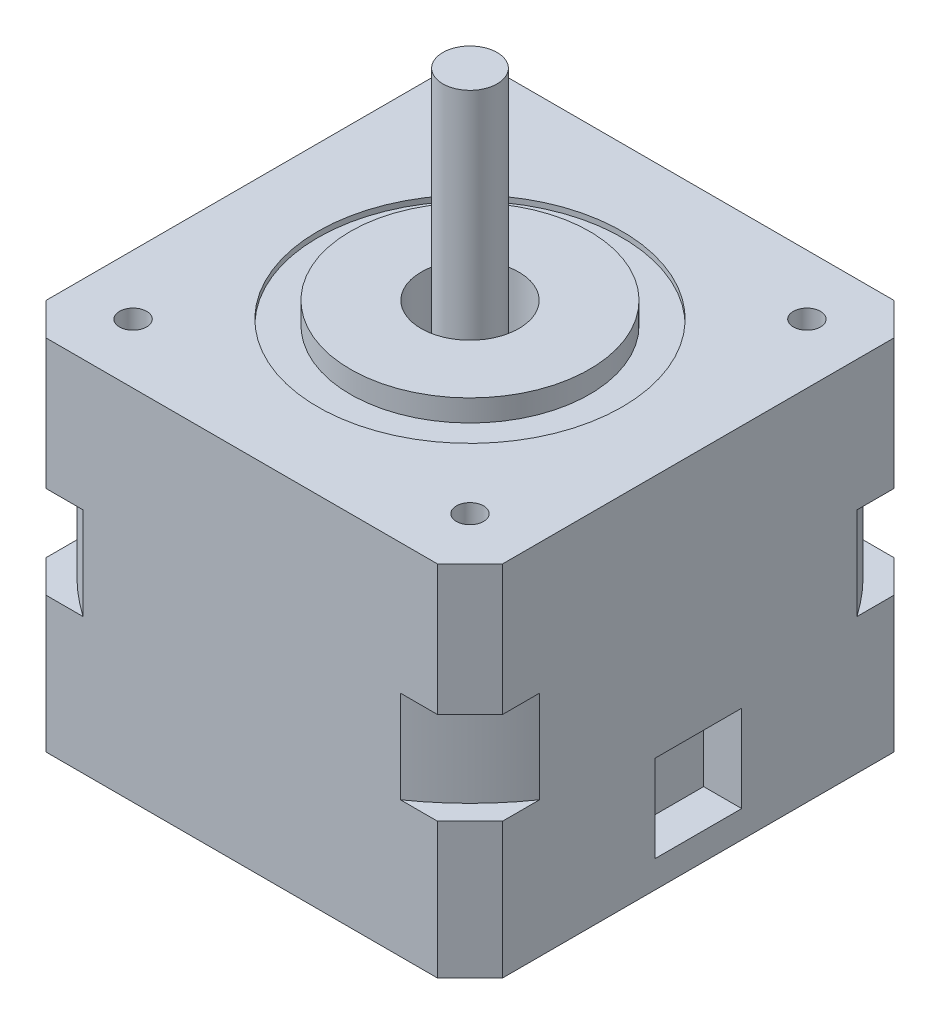
SolidWorks part; units mm, degrees
ref_plane "Front Plane" through (0, 0, 0) normal (0, 0, 1) x (1, 0, 0)
ref_plane "Top Plane" through (0, 0, 0) normal (0, 1, 0) x (1, 0, 0)
ref_plane "Right Plane" through (0, 0, 0) normal (1, 0, 0) x (0, 0, -1)
sketch "Sketch1" plane through (0, 0, 0) normal (0, 1, 0) x (1, 0, 0)
  line L0 (-18, 21) -> (-21, 18)
  line L1 (18, 21) -> (-18, 21)
  line L2 (21, 18) -> (21, -18)
  line L3 (18, -21) -> (-18, -21)
  line L4 (-21, 18) -> (-21, -18)
  line L5 (21, 21) -> (-21, -21) construction
  line L6 (21, -21) -> (-21, 21) construction
  line L7 (-21, -18) -> (-18, -21)
  line L8 (21, -18) -> (18, -21)
  line L9 (21, 18) -> (18, 21)
  point P0 (0, 0)
  point P14 (-21, -11.1783)
  dimension "D1" = 42
  dimension "D2" = 42
extrude "Boss-Extrude1" add sketch "Sketch1" along normal blind 33
ref_plane "Plane1" through (0, 0, 0) normal (0.7071, 0, 0.7071) x (0.7071, 0, -0.7071)
sketch "Sketch3" plane through (0, 0, 0) normal (0.7071, 0, 0.7071) x (0.7071, 0, -0.7071)
  line L0 (0, 33) -> (0, 0) construction
  line L1 (-2.1213, 33) -> (2.1213, 33) construction
  line L2 (27.5772, 21) -> (25.5772, 21)
  line L3 (27.5772, 33) -> (27.5772, 0) construction
  line L4 (25.5772, 21) -> (25.5772, 12.5)
  line L5 (25.5772, 12.5) -> (27.5772, 12.5)
  line L6 (2.1213, 0) -> (27.5772, 0) construction
  line L7 (2.1213, 33) -> (27.5772, 33) construction
  line L8 (14, 33) -> (14, 32.5)
  line L9 (27.5772, 21) -> (29.3552, 21)
  line L10 (29.3552, 21) -> (29.3552, 12.5)
  line L11 (29.3552, 12.5) -> (27.5772, 12.5)
  line L12 (14, 32.5) -> (11, 32.5)
  line L13 (11, 32.5) -> (11, 33)
  line L14 (11, 33) -> (14, 33)
  line L15 (4.5, 33) -> (4.5, 28)
  line L16 (4.5, 28) -> (0, 28)
  line L17 (0, 33) -> (4.5, 33)
  point P10 (26.5772, 12.5)
  dimension "D1" = 12.5
  dimension "D2" = 12
  dimension "D3" = 2
  dimension "D4" = 1.778
  dimension "D5" = 0.5
  dimension "D6" = 11
  dimension "D7" = 3
  dimension "D8" = 4.5
  dimension "D9" = 5
revolve "Cut-Revolve2" cut sketch "Sketch3" angle 360 about L0 region at (1.591, 30.5, -1.591) region at (19.4215, 16.75, -19.4215)
sketch "Sketch4" plane through (0, 33, 0) normal (0, 1, 0) x (1, 0, 0)
  line L1 (15.5, -15.5) -> (-15.5, -15.5) construction
  line L2 (15.5, -15.5) -> (15.5, 15.5) construction
  line L3 (15.5, 15.5) -> (-15.5, 15.5) construction
  line L4 (-15.5, -15.5) -> (-15.5, 15.5) construction
  line L5 (15.5, -15.5) -> (-15.5, 15.5) construction
  line L6 (15.5, 15.5) -> (-15.5, -15.5) construction
  circle A0 centre (-15.5, 15.5) radius 1.25
  circle A1 centre (15.5, 15.5) radius 1.25
  circle A2 centre (15.5, -15.5) radius 1.25
  circle A3 centre (-15.5, -15.5) radius 1.25
  point P0 (0, 0)
  dimension "D1" = 2.5
  dimension "D2" = 28.5
extrude "Cut-Extrude1" cut sketch "Sketch4" against normal through all
sketch "Sketch5" plane through (0, 0, 0) normal (0, -1, 0) x (1, 0, 0)
  circle A4 centre (-15.5, -15.5) radius 1.25 construction
  circle A5 centre (15.5, -15.5) radius 1.25 construction
  circle A6 centre (15.5, 15.5) radius 1.25 construction
  circle A7 centre (-15.5, 15.5) radius 1.25 construction
  circle A8 centre (-15.5, 15.5) radius 3.25
  circle A9 centre (-15.5, -15.5) radius 3.25
  circle A10 centre (15.5, -15.5) radius 3.25
  circle A11 centre (15.5, 15.5) radius 3.25
  circle A12 centre (0, 0) radius 4.75
  circle A13 centre (15.5, 15.5) radius 1.25 construction
  circle A14 centre (-15.5, 15.5) radius 1.25 construction
  circle A15 centre (-15.5, -15.5) radius 1.25 construction
  circle A16 centre (15.5, -15.5) radius 1.25 construction
  point P5 (15.5, 15.5)
  dimension "D1" = 6.5
  dimension "D2" = 9.5
extrude "Cut-Extrude2" cut sketch "Sketch5" against normal blind 3.5
sketch "Sketch6" plane through (21, 0, 0) normal (1, 0, 0) x (0, 0, -1)
  line L1 (-4, 2.5) -> (4, 2.5)
  line L2 (-4, 2.5) -> (-4, 10.5)
  line L3 (-4, 10.5) -> (4, 10.5)
  line L4 (4, 2.5) -> (4, 10.5)
  line L5 (-18, 0) -> (18, 0) construction
  point P4 (-4, 1.8272)
  point P6 (0, 10.5)
  point P8 (5.4752, 9.2137)
  dimension "D1" = 8
  dimension "D2" = 2.5
extrude "Cut-Extrude3" cut sketch "Sketch6" against normal blind 3.5
sketch "Sketch7" plane through (0, 0, 0) normal (0.7071, 0, 0.7071) x (0.7071, 0, -0.7071)
  line L0 (0, 33) -> (0, 0) construction
  line L1 (-2.1213, 33) -> (2.1213, 33) construction
  line L2 (4.5, 34.5) -> (11, 34.5)
  line L3 (11, 34.5) -> (11, 33)
  line L4 (2.1213, 33) -> (27.5772, 33) construction
  line L6 (4.5, 34.5) -> (4.5, 33)
  line L7 (4.5, 33) -> (11, 33)
  line L8 (0, 53) -> (2.5, 53)
  line L9 (2.5, 53) -> (2.5, 28)
  line L10 (4.5, 28) -> (-4.5, 28) construction
  line L11 (2.5, 28) -> (0, 28)
  line L13 (0, 53) -> (0, 28)
  dimension "D1" = 1.5
  dimension "D2" = 2.5
  dimension "D3" = 25
revolve "Revolve1" add sketch "Sketch7" angle 360 about L0
sketch "Sketch8" plane through (0, 0, 0) normal (0, -1, 0) x (1, 0, 0)
  circle A1 centre (-15.5, 15.5) radius 1.25 construction
  circle A2 centre (-15.5, 15.5) radius 1.25
  circle A3 centre (-15.5, -15.5) radius 1.25 construction
  circle A4 centre (15.5, -15.5) radius 1.25 construction
  circle A5 centre (15.5, 15.5) radius 1.25 construction
  circle A6 centre (-15.5, -15.5) radius 1.25
  circle A7 centre (15.5, -15.5) radius 1.25
  circle A8 centre (15.5, 15.5) radius 1.25
  circle A23 centre (-15.5, 15.5) radius 2.742
  circle A24 centre (-15.5, 15.5) radius 2.742
  circle A26 centre (-15.5, -15.5) radius 2.742
  circle A27 centre (-15.5, -15.5) radius 2.742
  circle A29 centre (15.5, -15.5) radius 2.742
  circle A30 centre (15.5, -15.5) radius 2.742
  circle A32 centre (15.5, 15.5) radius 2.742
  circle A33 centre (15.5, 15.5) radius 2.742
  dimension "D1" = 0.508
  dimension "D3" = 0.508
  dimension "D4" = 0.508
  dimension "D5" = 0.508
extrude "Boss-Extrude2" add sketch "Sketch8" against normal offset from surface (2.992 mm away) 0.508 separate body contours A2 | A24 A2 | A33 A8 | A8 | A30 A7 | A7 | A27 A6 | A6 region at (-15.5, 0, 15.5) region at (-15.5, 0, -15.5) region at (15.5, 0, -15.5) region at (15.5, 0, 15.5) region at (-18.1644, 0, 15.5) region at (-18.1644, 0, -15.5) region at (12.8356, 0, -15.5) region at (12.8356, 0, 15.5) up to face at (-15.5, 3.5, 12.25)
extrude "Boss-Extrude3" add sketch "Sketch8<3>" against normal blind 21.336 contours A2 | A6 | A7 | A8 region at (-15.5, 0, 15.5) region at (-15.5, 0, -15.5) region at (15.5, 0, -15.5) region at (15.5, 0, 15.5)
sketch "Sketch8<3>" plane through (0, 0, 0) normal (0, -1, 0) x (1, 0, 0) same geometry as "Sketch8"
sketch "Sketch9" plane through (0, 0, 0) normal (0, -1, 0) x (1, 0, 0)
  line L0 (18.242, -15.5) -> (12.758, -15.5) construction
  line L1 (15.5, -18.242) -> (15.5, -12.758) construction
  line L2 (18.134, -16.262) -> (16.262, -16.262)
  line L3 (16.262, -16.262) -> (16.262, -18.134)
  line L4 (16.262, -14.738) -> (16.262, -12.866)
  line L5 (18.134, -14.738) -> (16.262, -14.738)
  line L6 (14.738, -16.262) -> (14.738, -18.134)
  line L7 (12.866, -16.262) -> (14.738, -16.262)
  line L8 (14.738, -14.738) -> (14.738, -12.866)
  line L9 (12.866, -14.738) -> (14.738, -14.738)
  line L10 (0, -21) -> (0, 21) construction
  line L11 (18, -21) -> (-18, -21) construction
  line L12 (-18, 21) -> (18, 21) construction
  line L13 (21, 0) -> (-21, 0) construction
  line L14 (21, 18) -> (21, -18) construction
  line L15 (-21, -18) -> (-21, 18) construction
  line L16 (-15.5, -18.242) -> (-15.5, -12.758) construction
  line L17 (-18.242, -15.5) -> (-12.758, -15.5) construction
  line L18 (-12.866, -14.738) -> (-14.738, -14.738)
  line L19 (-14.738, -14.738) -> (-14.738, -12.866)
  line L20 (-12.866, -16.262) -> (-14.738, -16.262)
  line L21 (-14.738, -16.262) -> (-14.738, -18.134)
  line L22 (-18.134, -14.738) -> (-16.262, -14.738)
  line L23 (-16.262, -14.738) -> (-16.262, -12.866)
  line L24 (-16.262, -16.262) -> (-16.262, -18.134)
  line L25 (-18.134, -16.262) -> (-16.262, -16.262)
  line L26 (-18.242, 15.5) -> (-12.758, 15.5) construction
  line L27 (-15.5, 18.242) -> (-15.5, 12.758) construction
  line L28 (-18.134, 16.262) -> (-16.262, 16.262)
  line L29 (-16.262, 16.262) -> (-16.262, 18.134)
  line L30 (-16.262, 14.738) -> (-16.262, 12.866)
  line L31 (-18.134, 14.738) -> (-16.262, 14.738)
  line L32 (-14.738, 16.262) -> (-14.738, 18.134)
  line L33 (-12.866, 16.262) -> (-14.738, 16.262)
  line L34 (-14.738, 14.738) -> (-14.738, 12.866)
  line L35 (-12.866, 14.738) -> (-14.738, 14.738)
  line L36 (15.5, 18.242) -> (15.5, 12.758) construction
  line L37 (18.242, 15.5) -> (12.758, 15.5) construction
  line L38 (12.866, 14.738) -> (14.738, 14.738)
  line L39 (14.738, 14.738) -> (14.738, 12.866)
  line L40 (12.866, 16.262) -> (14.738, 16.262)
  line L41 (14.738, 16.262) -> (14.738, 18.134)
  line L42 (18.134, 14.738) -> (16.262, 14.738)
  line L43 (16.262, 14.738) -> (16.262, 12.866)
  line L44 (16.262, 16.262) -> (16.262, 18.134)
  line L45 (18.134, 16.262) -> (16.262, 16.262)
  circle A0 centre (15.5, -15.5) radius 2.742 construction
  circle A1 centre (15.5, -15.5) radius 2.742
  circle A2 centre (-15.5, -15.5) radius 2.742
  circle A3 centre (-15.5, 15.5) radius 2.742
  circle A4 centre (15.5, 15.5) radius 2.742
  point P4 (15.5, -15.5)
  point P5 (15.5, -15.5)
  circle M9 centre (15.5, -15.5) radius 2.742
  dimension "D1" = 0.762
  dimension "D2" = 0.762
extrude "Cut-Extrude4" cut sketch "Sketch9" against normal blind 1.016 contours L9 L7 L6 L3 L2 L5 L4 L8 M9 | A2 L25 L24 L21 L20 L18 L19 L23 L22 | L35 A3 L33 L32 L29 L28 L31 L30 L34 | A4 L38 L39 L43 L42 L45 L44 L41 L40 region at (15.5, 0, -15.5) region at (-15.5, 0, -15.5) region at (-15.5, 0, 15.5) region at (15.5, 0, 15.5)
